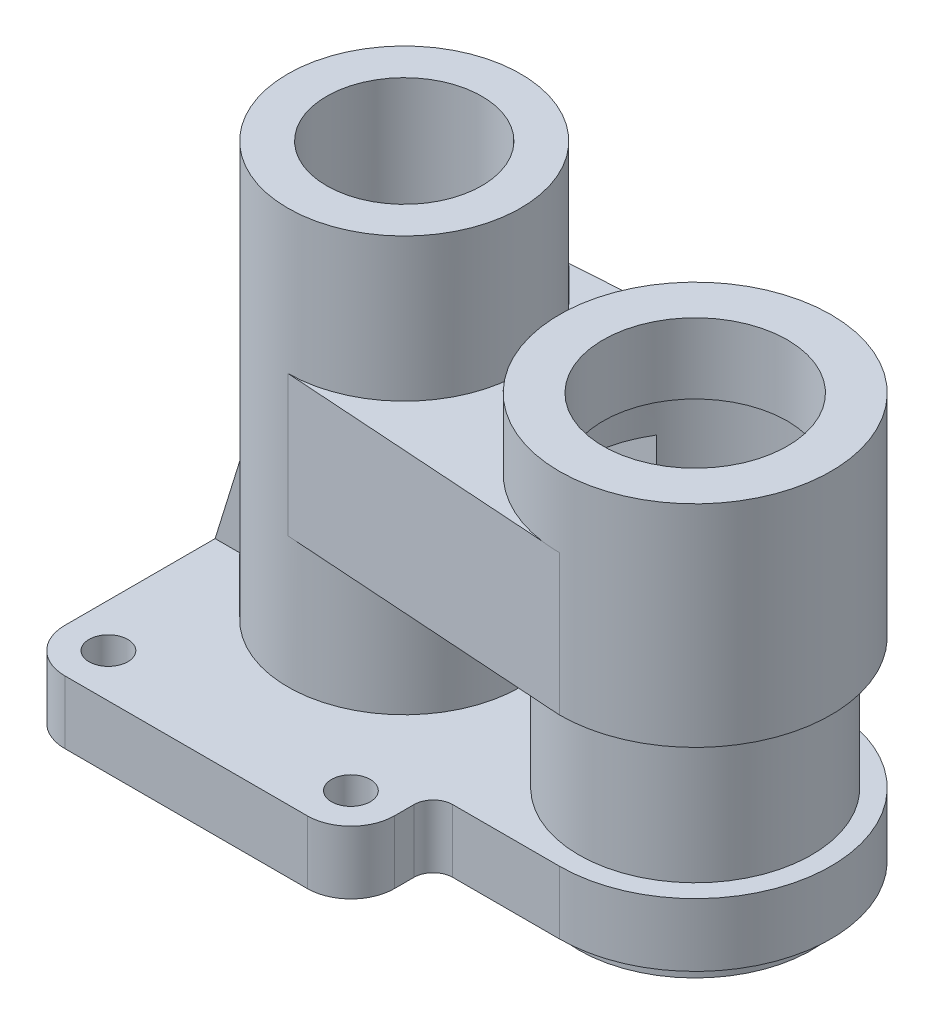
SolidWorks part; units mm, degrees
ref_plane "Front Plane" through (0, 0, 0) normal (0, 0, 1) x (1, 0, 0)
ref_plane "Top Plane" through (0, 0, 0) normal (0, 1, 0) x (1, 0, 0)
ref_plane "Right Plane" through (0, 0, 0) normal (1, 0, 0) x (0, 0, -1)
sketch "Sketch3" plane through (0, 0, 0) normal (0, 1, 0) x (1, 0, 0)
  line L0 (34, 28) -> (60, 28)
  line L1 (-34, 45) -> (34, 45)
  line L2 (-34, 45) -> (-34, -45)
  line L3 (-34, -45) -> (34, -45)
  line L4 (34, 45) -> (34, -45)
  line L5 (0, -45) -> (0, 45) construction
  line L6 (-34, 0) -> (34, 0) construction
  line L7 (60, -28) -> (34, -28)
  arc A0 (60, 28) -> (60, -28) centre (60, 0) cw
  point P0 (0, 0)
  dimension "D3" = 28
  dimension "D1" = 90
  dimension "D2" = 68
  dimension "D4" = 26
extrude "Boss-Extrude1" add sketch "Sketch3" along normal blind 13 contours L4 L1 L2 L3 | A0 L0 L4 L7 region at (0, 0, 0) region at (58.4025, 0, 0)
fillet "Fillet2" radius 4 2 edges at (34, 6.5, -28) (34, 6.5, 28)
fillet "Fillet3" radius 9 4 edges at (-34, 6.5, 45) (34, 6.5, 45) (34, 6.5, -45) (-34, 6.5, -45)
sketch "Sketch5" plane through (0, 13, 0) normal (0, 1, 0) x (1, 0, 0)
  circle A0 centre (-25, 36) radius 4
  circle A1 centre (25, 36) radius 4
  circle A2 centre (-25, -36) radius 4
  circle A3 centre (25, -36) radius 4
  dimension "D1" = 8
extrude "Cut-Extrude1" cut sketch "Sketch5" against normal through all
sketch "Sketch6" plane through (0, 0, 0) normal (0, 1, 0) x (1, 0, 0)
  circle A0 centre (0, 0) radius 16
  circle A1 centre (0, 0) radius 24
  circle A2 centre (60, 0) radius 28
  circle A3 centre (60, 0) radius 19
  dimension "D1" = 48
  dimension "D2" = 32
  dimension "D3" = 56
  dimension "D4" = 38
extrude "Boss-Extrude2" add sketch "Sketch6" along normal blind 41.0644 contours A1 A0 region at (-23.3212, 0, 0)
sketch "Sketch7" plane through (0, 13, 0) normal (0, 1, 0) x (1, 0, 0)
  circle A0 centre (60, 0) radius 24
  circle A1 centre (60, 0) radius 19
  dimension "D1" = 48
  dimension "D2" = 38
extrude "Boss-Extrude3" add sketch "Sketch7" against normal blind 17
extrude "Boss-Extrude4" add sketch "Sketch7<2>" along normal blind 28
sketch "Sketch7<2>" plane through (0, 13, 0) normal (0, 1, 0) x (1, 0, 0) same geometry as "Sketch7"
sketch "Sketch8" plane through (0, 41, 0) normal (0, 1, 0) x (1, 0, 0)
  line L0 (0, 24) -> (60, 28)
  line L1 (0, -24) -> (60, -28)
  circle A0 centre (0, 0) radius 16
  circle A1 centre (0, 0) radius 24
  circle A2 centre (60, 0) radius 28
  circle A3 centre (60, 0) radius 19
  circle A4 centre (0, 0) radius 16
  circle A5 centre (0, 0) radius 24
  circle M1 centre (60, 0) radius 24
  dimension "D1" = 56
  dimension "D2" = 38
extrude "Boss-Extrude11" add sketch "Sketch8" along normal blind 28 and the other way blind 1 contours A1 A0 | L1 A2 L0 M1 | A2 L0 A1 L1 region at (27.9935, 41, 0) region at (16.4906, 41, -16.4906) region at (58.1943, 41, -27.0859)
sketch "Sketch9" plane through (0, 0, 0) normal (0, 0, 1) x (1, 0, 0)
  line L0 (-24, 69) -> (-24, 13) construction
  line L1 (-16, 59.5) -> (79, 59.5)
  line L2 (-16, 59.5) -> (-16, 47.5)
  line L3 (-16, 47.5) -> (79, 47.5)
  line L4 (79, 59.5) -> (79, 47.5)
  line L5 (60, 40) -> (88, 40) construction
  point P0 (26.8207, 55.0328)
  dimension "D1" = 8
  dimension "D2" = 9
  dimension "D3" = 7.5
  dimension "D4" = 12
extrude "Cut-Extrude2" cut sketch "Sketch9" against normal mid plane 25
sketch "Sketch10" plane through (0, 69, 0) normal (0, 1, 0) x (1, 0, 0)
  circle A0 centre (0, 0) radius 16
  circle A2 centre (0, 0) radius 24
  dimension "D1" = 32
  dimension "D2" = 48
extrude "Boss-Extrude12" add sketch "Sketch10" along normal blind 29.5
ref_plane "Plane1" through (0, 69, 0) normal (0, 1, 0) x (1, 0, 0)
sketch "Sketch12" plane through (0, 69, 0) normal (0, 1, 0) x (1, 0, 0)
  circle A0 centre (60, 0) radius 19
  circle A1 centre (60, 0) radius 28
  dimension "D1" = 38
  dimension "D2" = 56
extrude "Boss-Extrude13" add sketch "Sketch12" along normal blind 14.5
sketch "Sketch13" plane through (0, 0, 0) normal (0, 0, 1) x (1, 0, 0)
  line L0 (-34, 13) -> (-23, 48.4669)
  line L1 (-24, 98.5) -> (-24, 13) construction
  dimension "D1" = 1
rib "Rib1" sketch "Sketch13" sketch "Sketch13" thickness 10 extrusion direction parallel to sketch draft on no parameters "D1"=10
sketch "Sketch15" plane through (0, 0, 0) normal (0, 1, 0) x (1, 0, 0)
  circle A0 centre (0, 0) radius 15.8292
  circle A1 centre (60, 0) radius 19
  dimension "D1" = 38
  dimension "D2" = 31.6583
extrude "Cut-Extrude5" cut sketch "Sketch15" along normal through all
